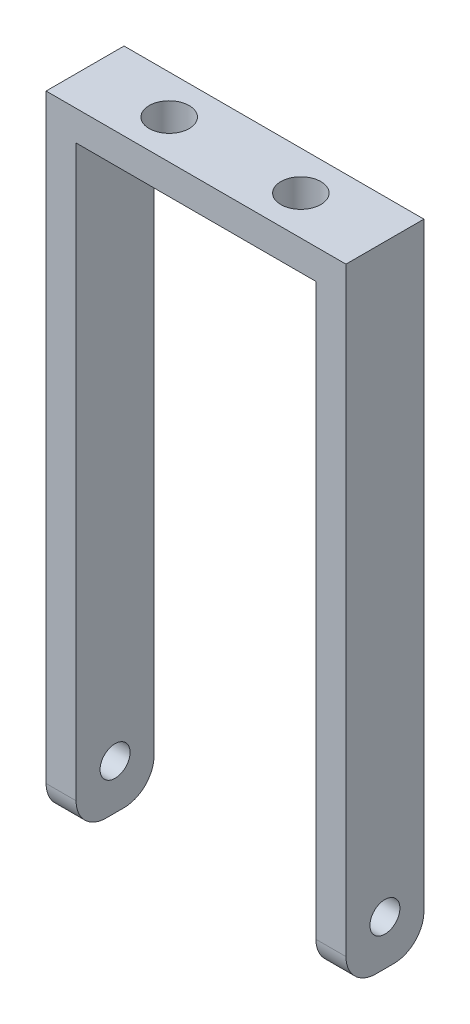
SolidWorks part; units mm, degrees
ref_plane "Front Plane" through (0, 0, 0) normal (0, 0, 1) x (1, 0, 0)
ref_plane "Top Plane" through (0, 0, 0) normal (0, 1, 0) x (1, 0, 0)
ref_plane "Right Plane" through (0, 0, 0) normal (1, 0, 0) x (0, 0, -1)
sketch "Sketch1" plane through (0, 0, 0) normal (0, 1, 0) x (1, 0, 0)
  line L1 (-15, -3.9) -> (15, -3.9)
  line L2 (-15, -3.9) -> (-15, 3.9)
  line L3 (-15, 3.9) -> (15, 3.9)
  line L4 (15, -3.9) -> (15, 3.9)
  line L5 (-15, -3.9) -> (15, 3.9) construction
  line L6 (-15, 3.9) -> (15, -3.9) construction
  point P0 (0, 0)
  dimension "D1" = 7.8
  dimension "D2" = 30
extrude "Boss-Extrude1" add sketch "Sketch1" against normal blind 3
sketch "Sketch2" plane through (0, 0, 0) normal (0, 1, 0) x (1, 0, 0)
  line L0 (-6.585, 0) -> (6.585, 0) construction
  circle A0 centre (-6.585, 0) radius 2
  circle A1 centre (6.585, 0) radius 2
  point P4 (0, 0)
extrude "Cut-Extrude1" cut sketch "Sketch2" against normal up to next
sketch "Sketch3" plane through (0, -3, 0) normal (0, -1, 0) x (1, 0, 0)
  line L0 (15, -3.9) -> (-15, -3.9) construction
  line L1 (-15, 3.9) -> (-12, 3.9)
  line L2 (-15, 3.9) -> (-15, -3.9)
  line L3 (-15, -3.9) -> (-12, -3.9)
  line L4 (-12, 3.9) -> (-12, -3.9)
  line L6 (15, 3.9) -> (12, 3.9)
  line L7 (15, 3.9) -> (15, -3.9)
  line L8 (15, -3.9) -> (12, -3.9)
  line L9 (12, 3.9) -> (12, -3.9)
  dimension "D1" = 3
  dimension "D2" = 3
extrude "Boss-Extrude2" add sketch "Sketch3" along normal blind 60
sketch "Sketch4" plane through (15, 0, 0) normal (1, 0, 0) x (0, 0, -1)
  line L0 (0, -63) -> (0, -58.5) construction
  line L1 (3.9, -63) -> (-3.9, -63) construction
  circle A1 centre (0, -58.5) radius 1.5
extrude "Cut-Extrude2" cut sketch "Sketch4" against normal through all both and the other way through all
fillet "Fillet1" radius 3 4 edges at (-13.5, -63, -3.9) (13.5, -63, -3.9) (-13.5, -63, 3.9) (13.5, -63, 3.9)
